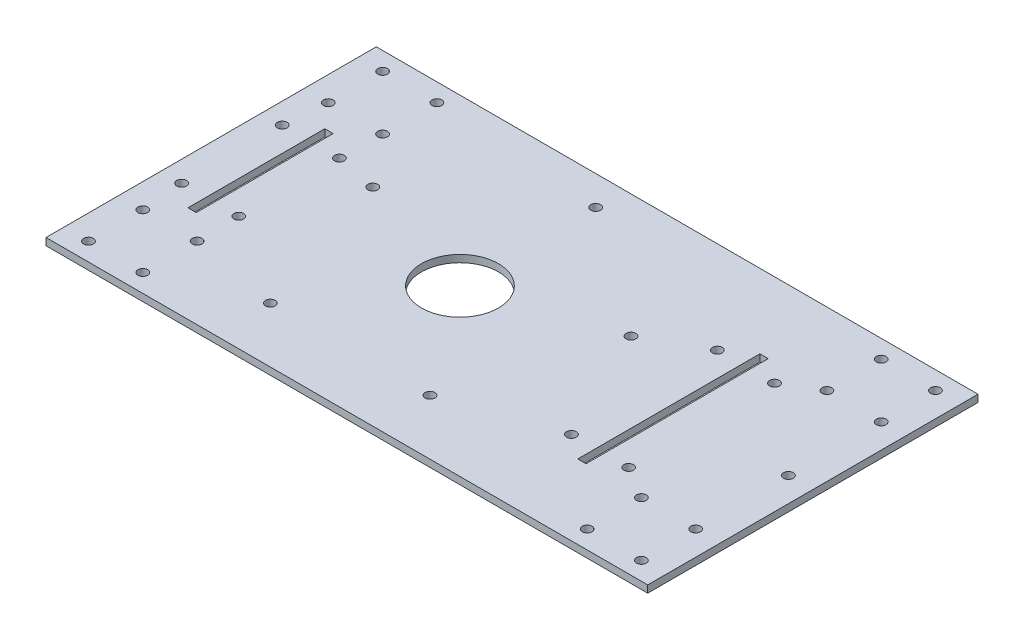
SolidWorks part; units mm, degrees
ref_plane "Front Plane" through (0, 0, 0) normal (0, 0, 1) x (1, 0, 0)
ref_plane "Top Plane" through (0, 0, 0) normal (0, 1, 0) x (1, 0, 0)
ref_plane "Right Plane" through (0, 0, 0) normal (1, 0, 0) x (0, 0, -1)
sketch "Sketch2" plane through (0, 0, 0) normal (0, 1, 0) x (1, 0, 0)
  line L0 (0, 73) -> (266, 73) construction
  line L1 (0, 0) -> (266, 0)
  line L2 (0, 0) -> (0, 146)
  line L3 (0, 146) -> (266, 146)
  line L4 (266, 0) -> (266, 146)
  line L5 (133, 146) -> (133, 0) construction
  line L6 (110, 146) -> (110, 0) construction
  line L7 (6.9839, 20) -> (45.1328, 20) construction
  line L8 (259.0161, 20) -> (220.8672, 20) construction
  line L9 (204.1625, 113.25) -> (204.1625, 32.75) construction
  line L10 (202.325, 32.75) -> (206, 32.75)
  line L11 (202.325, 32.75) -> (202.325, 113.25)
  line L12 (202.325, 113.25) -> (206, 113.25)
  line L13 (206, 32.75) -> (206, 113.25)
  line L14 (202.325, 32.75) -> (206, 113.25) construction
  line L15 (202.325, 113.25) -> (206, 32.75) construction
  line L16 (21.8375, 103.25) -> (21.8375, 42.75) construction
  line L17 (20, 42.75) -> (23.675, 42.75)
  line L18 (20, 42.75) -> (20, 103.25)
  line L19 (20, 103.25) -> (23.675, 103.25)
  line L20 (23.675, 42.75) -> (23.675, 103.25)
  line L21 (20, 42.75) -> (23.675, 103.25) construction
  line L22 (20, 103.25) -> (23.675, 42.75) construction
  circle A0 centre (110, 133) radius 2.15
  circle A1 centre (167.0634, 91.541) radius 2.15
  circle A2 centre (145.2671, 24.459) radius 2.15
  circle A3 centre (74.7329, 24.459) radius 2.15
  circle A4 centre (52.9366, 91.541) radius 2.15
  circle A5 centre (10.8, 8) radius 2.15
  circle A15 centre (10.8, 138) radius 2.15
  circle A22 centre (34.8, 8) radius 2.15
  circle A26 centre (34.8, 138) radius 2.15
  circle A32 centre (9.2, 50.75) radius 2.15
  circle A33 centre (9.2, 95.25) radius 2.15
  circle A44 centre (34.475, 50.75) radius 2.15
  circle A45 centre (34.8, 32) radius 2.15
  circle A54 centre (34.8, 114) radius 2.15
  circle A55 centre (10.8, 32) radius 2.15
  circle A56 centre (10.8, 114) radius 2.15
  circle A57 centre (231.2, 138) radius 2.15
  circle A58 centre (231.2, 114) radius 2.15
  circle A59 centre (255.2, 114) radius 2.15
  circle A60 centre (255.2, 138) radius 2.15
  circle A61 centre (255.2, 73) radius 2.15
  circle A62 centre (231.2, 32) radius 2.15
  circle A63 centre (255.2, 32) radius 2.15
  circle A64 centre (231.2, 8) radius 2.15
  circle A65 centre (255.2, 8) radius 2.15
  circle A66 centre (110, 73) radius 17
  circle A67 centre (216.8, 40.75) radius 2.15
  circle A68 centre (216.8, 105.25) radius 2.15
  circle A69 centre (191.525, 40.75) radius 2.15
  circle A70 centre (191.525, 105.25) radius 2.15
  circle A71 centre (34.475, 95.25) radius 2.15
  point P13 (110, 73)
  point P24 (110, 73)
  point P69 (204.1625, 73)
  point P86 (21.8375, 73)
  dimension "D4" = 4.3
  dimension "D7" = 4.3
  dimension "D10" = 4.3
  dimension "D12" = 34
  dimension "D18" = 4.3
  dimension "D1" = 266
  dimension "D2" = 146
  dimension "D3" = 110
  dimension "D5" = 60
  dimension "D8" = 10.8
  dimension "D9" = 8
  dimension "D11" = 2
  dimension "D13" = 3.675
  dimension "D14" = 80.5
  dimension "D15" = 24
  dimension "D16" = 12
  dimension "D17" = 60
  dimension "D19" = 8
  dimension "D20" = 10.8
  dimension "D21" = 3.675
  dimension "D22" = 60.5
  dimension "D23" = 20
  dimension "D24" = 8
  dimension "D25" = 10.8
  dimension "D6" = 5
extrude "Boss-Extrude2" add sketch "Sketch2" along normal blind 3.175
